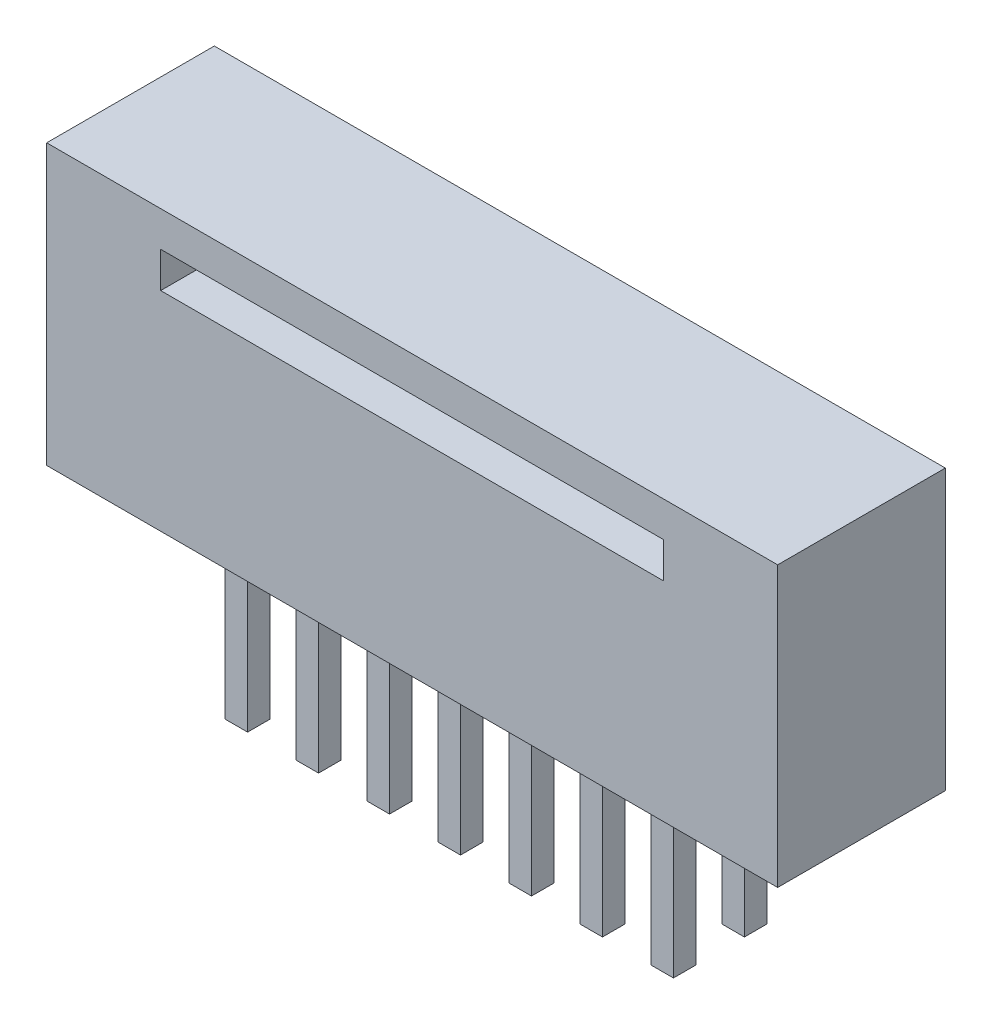
SolidWorks part; units mm, degrees
ref_plane "Front Plane" through (0, 0, 0) normal (0, 0, 1) x (1, 0, 0)
ref_plane "Top Plane" through (0, 0, 0) normal (0, 1, 0) x (1, 0, 0)
ref_plane "Right Plane" through (0, 0, 0) normal (1, 0, 0) x (0, 0, -1)
sketch "Sketch1" plane through (0, 0, 0) normal (0, 1, 0) x (1, 0, 0)
  line L0 (-2.74, -0.835) -> (-2.34, -0.835)
  line L1 (-4.01, -0.435) -> (-3.61, -0.435)
  line L2 (-4.01, -0.435) -> (-4.01, -0.835)
  line L3 (-4.01, -0.835) -> (-3.61, -0.835)
  line L4 (-3.61, -0.435) -> (-3.61, -0.835)
  line L5 (-4.01, -0.435) -> (-3.61, -0.835) construction
  line L6 (-4.01, -0.835) -> (-3.61, -0.435) construction
  line L7 (-2.74, -0.435) -> (-2.74, -0.835)
  line L8 (-2.74, -0.435) -> (-2.34, -0.435)
  line L9 (-2.34, -0.435) -> (-2.34, -0.835)
  line L10 (-1.47, -0.835) -> (-1.07, -0.835)
  line L11 (-1.47, -0.435) -> (-1.47, -0.835)
  line L12 (-1.47, -0.435) -> (-1.07, -0.435)
  line L13 (-1.07, -0.435) -> (-1.07, -0.835)
  line L14 (-0.2, -0.835) -> (0.2, -0.835)
  line L15 (-0.2, -0.435) -> (-0.2, -0.835)
  line L16 (-0.2, -0.435) -> (0.2, -0.435)
  line L17 (0.2, -0.435) -> (0.2, -0.835)
  line L18 (1.07, -0.835) -> (1.47, -0.835)
  line L19 (1.07, -0.435) -> (1.07, -0.835)
  line L20 (1.07, -0.435) -> (1.47, -0.435)
  line L21 (1.47, -0.435) -> (1.47, -0.835)
  line L22 (2.34, -0.835) -> (2.74, -0.835)
  line L23 (2.34, -0.435) -> (2.34, -0.835)
  line L24 (2.34, -0.435) -> (2.74, -0.435)
  line L25 (2.74, -0.435) -> (2.74, -0.835)
  line L26 (3.61, -0.835) -> (4.01, -0.835)
  line L27 (3.61, -0.435) -> (3.61, -0.835)
  line L28 (3.61, -0.435) -> (4.01, -0.435)
  line L29 (4.01, -0.435) -> (4.01, -0.835)
  line L30 (-2.74, 0.435) -> (-2.34, 0.435)
  line L31 (-2.74, 0.835) -> (-2.74, 0.435)
  line L32 (-2.74, 0.835) -> (-2.34, 0.835)
  line L33 (-2.34, 0.835) -> (-2.34, 0.435)
  line L34 (-1.47, 0.435) -> (-1.07, 0.435)
  line L35 (-1.47, 0.835) -> (-1.47, 0.435)
  line L36 (-1.47, 0.835) -> (-1.07, 0.835)
  line L37 (-1.07, 0.835) -> (-1.07, 0.435)
  line L38 (-0.2, 0.435) -> (0.2, 0.435)
  line L39 (-0.2, 0.835) -> (-0.2, 0.435)
  line L40 (-0.2, 0.835) -> (0.2, 0.835)
  line L41 (0.2, 0.835) -> (0.2, 0.435)
  line L42 (1.07, 0.435) -> (1.47, 0.435)
  line L43 (1.07, 0.835) -> (1.07, 0.435)
  line L44 (1.07, 0.835) -> (1.47, 0.835)
  line L45 (1.47, 0.835) -> (1.47, 0.435)
  line L46 (2.34, 0.435) -> (2.74, 0.435)
  line L47 (2.34, 0.835) -> (2.34, 0.435)
  line L48 (2.34, 0.835) -> (2.74, 0.835)
  line L49 (2.74, 0.835) -> (2.74, 0.435)
  line L50 (3.61, 0.435) -> (4.01, 0.435)
  line L51 (3.61, 0.835) -> (3.61, 0.435)
  line L52 (3.61, 0.835) -> (4.01, 0.835)
  line L53 (4.01, 0.835) -> (4.01, 0.435)
  line L54 (-4.01, 0.435) -> (-3.61, 0.435)
  line L55 (-4.01, 0.835) -> (-4.01, 0.435)
  line L56 (-4.01, 0.835) -> (-3.61, 0.835)
  line L57 (-3.61, 0.835) -> (-3.61, 0.435)
  line L58 (-4.01, -0.835) -> (-2.74, -0.835) construction
  line L59 (-4.01, -0.835) -> (-4.01, 0.435) construction
  line L60 (3.61, 0.435) -> (4.01, 0.835) construction
  line L61 (4.01, 0.435) -> (3.61, 0.835) construction
  line L62 (3.81, 0.635) -> (-3.81, -0.635) construction
  point P0 (-3.81, -0.635)
  point P5 (3.81, 0.635)
  point P63 (0, 0)
  dimension "D1" = 0.4
  dimension "D2" = 0.4
  dimension "D5" = 90
  dimension "D6" = 1.27
  dimension "D7" = 1.27
  dimension "D3" = 7
  dimension "D4" = 2
extrude "Boss-Extrude1" add sketch "Sketch1" against normal blind 3
sketch "Sketch2" plane through (0, 0, 0) normal (0, 1, 0) x (1, 0, 0)
  line L1 (-6.54, 1.5) -> (6.54, 1.5)
  line L2 (-6.54, 1.5) -> (-6.54, -1.5)
  line L3 (-6.54, -1.5) -> (6.54, -1.5)
  line L4 (6.54, 1.5) -> (6.54, -1.5)
  line L5 (-6.54, 1.5) -> (6.54, -1.5) construction
  line L6 (-6.54, -1.5) -> (6.54, 1.5) construction
  point P0 (0, 0)
  dimension "D1" = 3
  dimension "D2" = 13.08
extrude "Boss-Extrude2" add sketch "Sketch2" along normal blind 5
sketch "Sketch3" plane through (0, 0, 1.5) normal (0, 0, 1) x (1, 0, 0)
  line L0 (-6.54, 5) -> (6.54, 5) construction
  line L1 (-4.5, 4.37) -> (4.5, 4.37)
  line L2 (-4.5, 4.37) -> (-4.5, 3.73)
  line L3 (-4.5, 3.73) -> (4.5, 3.73)
  line L4 (4.5, 4.37) -> (4.5, 3.73)
  line L5 (-4.5, 4.37) -> (4.5, 3.73) construction
  line L6 (-4.5, 3.73) -> (4.5, 4.37) construction
  point P0 (0, 4.05)
  point P5 (0, 5)
  dimension "D1" = 0.64
  dimension "D2" = 9
  dimension "D3" = 0.95
extrude "Cut-Extrude1" cut sketch "Sketch3" against normal through all
ref_axis "Cable mating axis" through (0, 4.05, 1.5) along (0, 0, 1)
equation "\"D1@Boss-Extrude2\"=3.1+1.9"
equation "\"D3@Sketch3\"=1.9/2"
